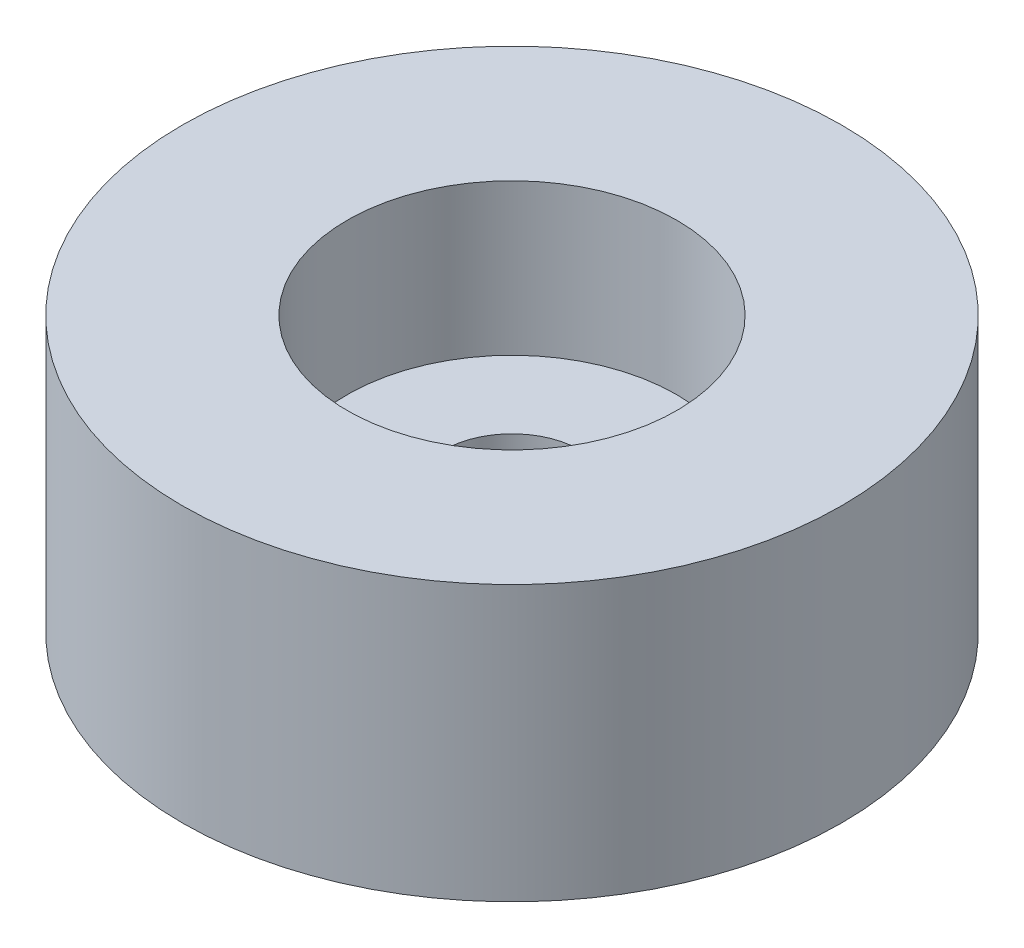
SolidWorks part; units mm, degrees
ref_plane "Front Plane" through (0, 0, 0) normal (0, 0, 1) x (1, 0, 0)
ref_plane "Top Plane" through (0, 0, 0) normal (0, 1, 0) x (1, 0, 0)
ref_plane "Right Plane" through (0, 0, 0) normal (1, 0, 0) x (0, 0, -1)
sketch "Sketch1" plane through (0, 0, 0) normal (0, 0, 1) x (1, 0, 0)
  line L0 (0, 0) -> (0, 22.6347) construction
  line L1 (3.9688, 0) -> (3.9688, 5.1437)
  line L2 (3.9688, 5.1437) -> (9.525, 5.1437)
  line L3 (9.525, 5.1437) -> (9.525, 7.1437)
  line L4 (9.525, 7.1437) -> (3.9688, 7.1437)
  line L5 (3.9688, 7.1437) -> (3.9688, 5.1437)
  line L6 (9.525, 7.1437) -> (9.525, 15.875)
  line L7 (9.525, 15.875) -> (19.05, 15.875)
  line L8 (19.05, 15.875) -> (19.05, 0)
  line L9 (19.05, 0) -> (3.9688, 0)
  point P2 (19.05, 17.3518)
  point P6 (2.1361, 0)
  point P13 (0, 0)
  dimension "D1" = 38.1
  dimension "D2" = 15.875
  dimension "D3" = 9.525
  dimension "D4" = 7.9375
  dimension "D5" = 2
  dimension "D6" = 7.1437
revolve "Revolve1" add sketch "Sketch1" angle 360 about L0 region at (13.0888, 7.0846, 0)
revolve "Revolve2" add sketch "Sketch1<4>" angle 360 about L0 region at (6.7469, 6.1437, 0)
sketch "Sketch1<4>" plane through (0, 0, 0) normal (0, 0, 1) x (1, 0, 0) same geometry as "Sketch1"
